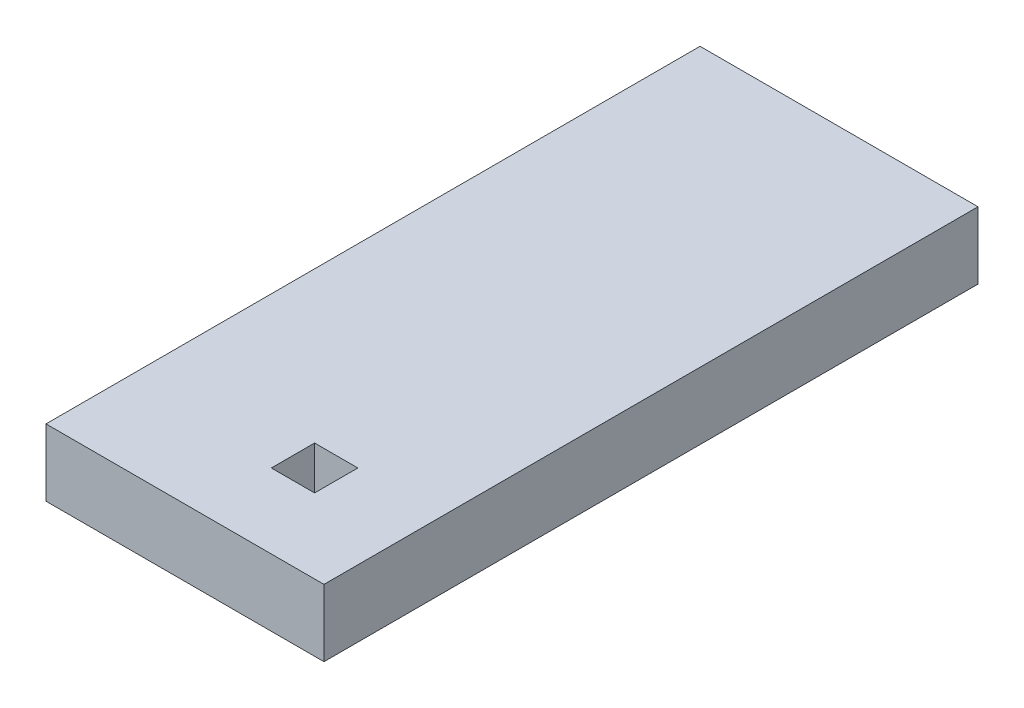
SolidWorks part; units mm, degrees
material "Acrylic (Medium-high impact)"
ref_plane "Front Plane" through (0, 0, 0) normal (0, 0, 1) x (1, 0, 0)
ref_plane "Top Plane" through (0, 0, 0) normal (0, 1, 0) x (1, 0, 0)
ref_plane "Right Plane" through (0, 0, 0) normal (1, 0, 0) x (0, 0, -1)
sketch "Sketch1" plane through (0, 0, 0) normal (0, 1, 0) x (1, 0, 0)
  line L0 (0, -10.9442) -> (0, 0) construction
  line L1 (5, -15.5) -> (-5, -15.5)
  line L2 (5, -15.5) -> (5, 15.5)
  line L3 (5, 15.5) -> (-5, 15.5)
  line L4 (-5, -15.5) -> (-5, 15.5)
  line L5 (5, -15.5) -> (-5, 15.5) construction
  line L6 (5, 15.5) -> (-5, -15.5) construction
  line L7 (-1.025, -9.9192) -> (1.025, -9.9192)
  line L8 (-1.025, -9.9192) -> (-1.025, -11.9692)
  line L9 (-1.025, -11.9692) -> (1.025, -11.9692)
  line L10 (1.025, -9.9192) -> (1.025, -11.9692)
  line L11 (-1.025, -9.9192) -> (1.025, -11.9692) construction
  line L12 (-1.025, -11.9692) -> (1.025, -9.9192) construction
  point P0 (0, 0)
  point P6 (0, -10.9442)
  dimension "D1" = 10
  dimension "D2" = 31
  dimension "D3" = 2.05
  dimension "D4" = 3.5308
extrude "Boss-Extrude1" add sketch "Sketch1" along normal blind 3.175 contours L1 L2 L3 L4 L7 L10 L9 L8 | L4 region at (0, 0, -0.1504)
sketch "Sketch2" plane through (0, 3.175, 0) normal (0, 1, 0) x (1, 0, 0)
  line L5 (5, -15.5) -> (-5, -15.5) construction
  line L6 (-5, 15.5) -> (-8.175, 15.5)
  line L7 (-5, 15.5) -> (-5, -15.5)
  line L8 (-5, -15.5) -> (-8.175, -15.5)
  line L9 (-8.175, 15.5) -> (-8.175, -15.5)
  dimension "D1" = 3.175
extrude "Boss-Extrude2" add sketch "Sketch2" against normal up to surface (3.175 mm away) up to face at (0, 0, 0)
equation "\"bottomThickness\"= .220in"
equation "\"wallThickness\"= .125in"
equation "\"D1@Boss-Extrude1\"=\"wallThickness\""
equation "\"D1@Sketch2\"=\"wallThickness\""
